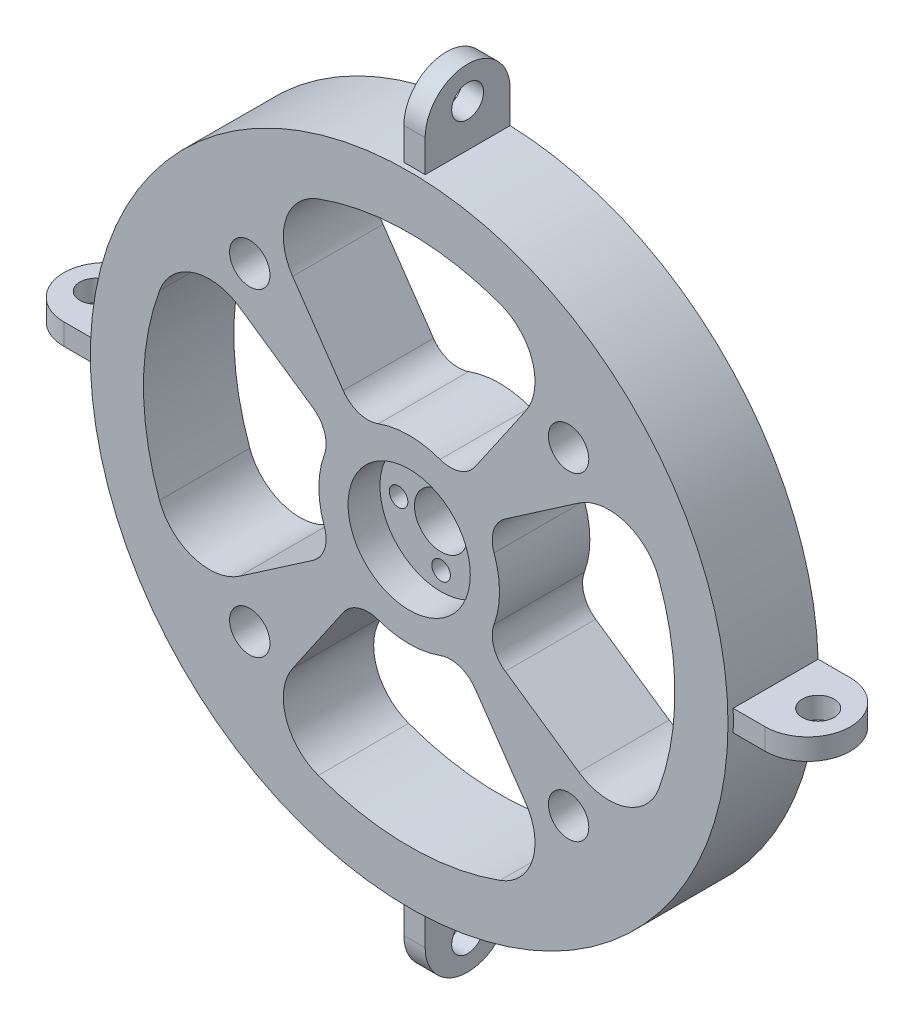
SolidWorks part; units mm, degrees
material "尼龙 101"
ref_plane "前视基准面" through (0, 0, 0) normal (0, 0, 1) x (1, 0, 0)
ref_plane "上视基准面" through (0, 0, 0) normal (0, 1, 0) x (1, 0, 0)
ref_plane "右视基准面" through (0, 0, 0) normal (1, 0, 0) x (0, 0, -1)
sketch "草图1" plane through (0, 0, 0) normal (0, 0, 1) x (1, 0, 0)
  circle A0 centre (0, 0) radius 60
  dimension "D1" = 120
extrude "凸台-拉伸1" add sketch "草图1" along normal blind 17
sketch "草图2" plane through (0, 0, 17) normal (0, 0, 1) x (1, 0, 0)
  line L0 (0, 30) -> (0, 0) construction
  line L1 (0, 0) -> (0, -30) construction
  line L2 (-30, 0) -> (0, 0) construction
  line L3 (0, 0) -> (30, 0) construction
  circle A4 centre (-30, 30) radius 3.8
  circle A5 centre (30, 30) radius 3.8
  circle A6 centre (30, -30) radius 3.8
  circle A7 centre (-30, -30) radius 3.8
  dimension "D1" = 7.6
  dimension "D2" = 7.6
  dimension "D7" = 7.6
  dimension "D8" = 7.6
  dimension "D3" = 30
  dimension "D4" = 30
  dimension "D5" = 30
  dimension "D6" = 30
  dimension "D9" = 60
  dimension "D10" = 60
extrude "切除-拉伸1" cut sketch "草图2" against normal through all
sketch "草图3" plane through (0, 0, 0) normal (1, 0, 0) x (0, 0, -1)
  line L0 (0, 58) -> (-16, 58)
  line L1 (-16, 58) -> (-16, 66)
  line L2 (0, 66) -> (0, 58)
  line L3 (0, 0) -> (-35.6052, 0) construction
  arc A0 (-16, 66) -> (0, 66) centre (-8, 66) cw
  dimension "D3" = 8
  dimension "D1" = 58
  dimension "D2" = 8
  dimension "D4" = 0
extrude "凸台-拉伸2" add sketch "草图3" along normal blind 2 and the other way blind 2
sketch "草图4" plane through (2, 0, 0) normal (1, 0, 0) x (0, 0, -1)
  line L0 (-16, 59.9667) -> (0, 59.9667) construction
  line L1 (0, 59.9667) -> (0, 66) construction
  circle A0 centre (-8, 67.9667) radius 3
  dimension "D1" = 6
  dimension "D2" = 8
  dimension "D3" = 8
extrude "切除-拉伸7" cut sketch "草图4" against normal through all
sketch "草图5" plane through (0, 0, 0) normal (0, 0, -1) x (-1, 0, 0)
  circle A0 centre (0, 0) radius 5
  dimension "D1" = 10
extrude "切除-拉伸3" cut sketch "草图5" against normal up to next
sketch "草图6" plane through (0, 0, 17) normal (0, 0, 1) x (1, 0, 0)
  circle A0 centre (0, 0) radius 11.5
  dimension "D1" = 23
extrude "切除-拉伸4" cut sketch "草图6" against normal blind 6
sketch "草图7" plane through (0, 0, 11) normal (0, 0, 1) x (1, 0, 0)
  circle A0 centre (0, 0) radius 8 construction
  circle A1 centre (-8, 0) radius 1.75
  circle A2 centre (0, 8) radius 1.75
  circle A3 centre (8, 0) radius 1.75
  circle A4 centre (0, -8) radius 1.75
  dimension "D1" = 16
  dimension "D2" = 3.5
  dimension "D3" = 3.5
  dimension "D4" = 3.5
  dimension "D5" = 3.5
extrude "切除-拉伸5" cut sketch "草图7" against normal up to next
sketch "草图8" plane through (0, 0, 17) normal (0, 0, 1) x (1, 0, 0)
  line L0 (-37.5877, -13.6808) -> (0, 0) construction
  line L1 (0, 0) -> (-37.5877, 13.6808) construction
  line L2 (0, 0) -> (-30, 0) construction
  line L3 (-37.5877, -13.6808) -> (-46.9846, -17.101) construction
  line L4 (-37.5877, 13.6808) -> (-46.9846, 17.101) construction
  line L13 (-18.0919, -12.4238) -> (0, 0) construction
  line L14 (-18.0919, 12.4238) -> (-31.9269, 21.9243)
  line L15 (-31.9269, -21.9243) -> (-18.0919, -12.4238)
  arc A0 (-37.5877, -13.6808) -> (-37.5877, 13.6808) centre (0, 0) cw construction
  arc A6 (-46.9846, -17.101) -> (-46.9846, 17.101) centre (0, 0) cw
  arc A7 (-46.9846, -17.101) -> (-31.9269, -21.9243) centre (-37.5877, -13.6808) ccw
  arc A9 (-15.9748, -5.8143) -> (-15.9748, 5.8143) centre (0, 0) cw
  arc A11 (-15.9748, -5.8143) -> (-18.0919, -12.4238) centre (-21.2997, -7.7525) cw
  arc A31 (-15.9748, 5.8143) -> (-18.0919, 12.4238) centre (-21.2997, 7.7525) ccw
  arc A32 (-46.9846, 17.101) -> (-31.9269, 21.9243) centre (-37.5877, 13.6808) cw
  dimension "D2" = 20
  dimension "D3" = 40
  dimension "D4" = 50
  dimension "D5" = 17
extrude "切除-拉伸6" cut sketch "草图8" against normal up to next
pattern_circular "阵列(圆周)3" count 4 over 360 about axis through (0, 0, 17) along (0, 0, 1) of "切除-拉伸6"
pattern_circular "阵列(圆周)4" count 4 over 360 about axis through (0, 0, 17) along (0, 0, 1) of "凸台-拉伸2", "切除-拉伸7"
